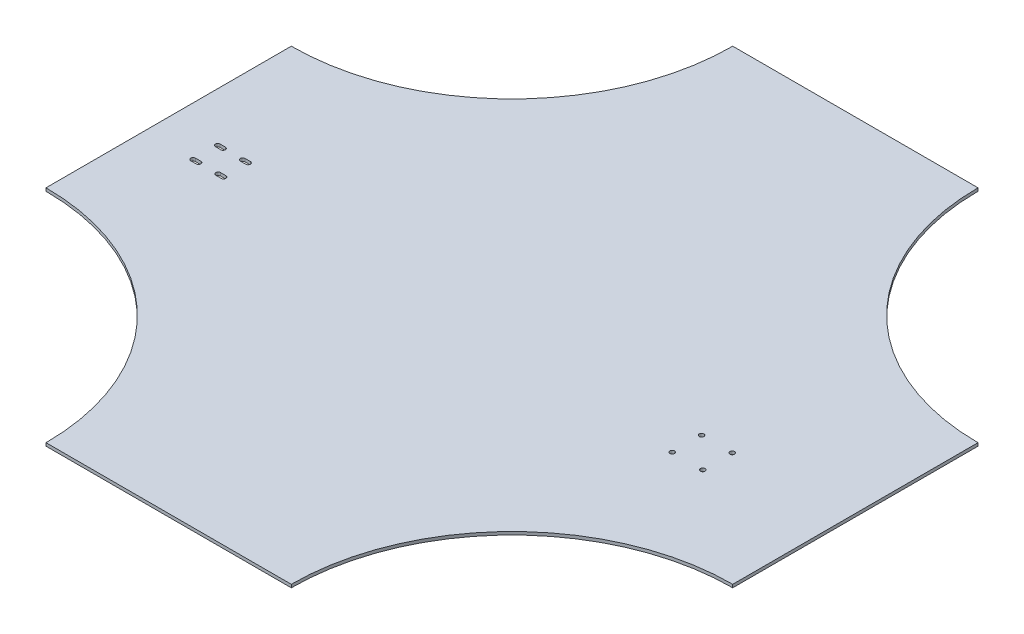
SolidWorks part; units mm, degrees
ref_plane "Front Plane" through (0, 0, 0) normal (0, 0, 1) x (1, 0, 0)
ref_plane "Top Plane" through (0, 0, 0) normal (0, 1, 0) x (1, 0, 0)
ref_plane "Right Plane" through (0, 0, 0) normal (1, 0, 0) x (0, 0, -1)
sketch "Sketch1" plane through (0, 0, 0) normal (0, 1, 0) x (1, 0, 0)
  line L9 (-127, -355.6) -> (127, -355.6)
  line L10 (-355.6, -127) -> (-355.6, 127)
  line L11 (-127, 355.6) -> (127, 355.6)
  line L12 (355.6, -127) -> (355.6, 127)
  line L13 (-193.9554, -193.9554) -> (193.9554, 193.9554) construction
  line L14 (-193.9554, 193.9554) -> (193.9554, -193.9554) construction
  arc A8 (-355.6, 127) -> (-127, 355.6) centre (-355.6, 355.6) ccw
  arc A9 (127, 355.6) -> (355.6, 127) centre (355.6, 355.6) ccw
  arc A10 (355.6, -127) -> (127, -355.6) centre (355.6, -355.6) ccw
  arc A11 (-127, -355.6) -> (-355.6, -127) centre (-355.6, -355.6) ccw
  point P0 (0, 0)
  point P1 (0, 0)
  point P2 (0, 0)
  dimension "D3" = 457.2
  dimension "D4" = 457.2
  dimension "D5" = 457.2
  dimension "D6" = 457.2
  dimension "D1" = 711.2
  dimension "D2" = 711.2
extrude "Boss-Extrude1" add sketch "Sketch1" along normal blind 3.175
sketch "Sketch2" plane through (0, 3.175, 0) normal (0, 1, 0) x (1, 0, 0)
  line L0 (-304.8, 2.413) -> (-299.212, 2.413)
  line L1 (-304.8, -22.987) -> (-299.212, -22.987)
  line L2 (-299.212, -2.413) -> (-304.8, -2.413)
  line L3 (-278.892, -2.413) -> (-273.304, -2.413)
  line L4 (-278.892, -22.987) -> (-273.304, -22.987)
  line L5 (-273.304, 2.413) -> (-278.892, 2.413)
  line L6 (-299.212, -27.813) -> (-304.8, -27.813)
  line L7 (-355.6, 127) -> (-355.6, -127) construction
  line L8 (-273.304, -27.813) -> (-278.892, -27.813)
  arc A0 (-299.212, -2.413) -> (-299.212, 2.413) centre (-299.212, 0) ccw
  arc A1 (-273.304, -2.413) -> (-273.304, 2.413) centre (-273.304, 0) ccw
  arc A2 (-273.304, -27.813) -> (-273.304, -22.987) centre (-273.304, -25.4) ccw
  arc A3 (-299.212, -27.813) -> (-299.212, -22.987) centre (-299.212, -25.4) ccw
  arc A4 (-278.892, 2.413) -> (-278.892, -2.413) centre (-278.892, 0) ccw
  arc A5 (-304.8, 2.413) -> (-304.8, -2.413) centre (-304.8, 0) ccw
  arc A6 (-304.8, -22.987) -> (-304.8, -27.813) centre (-304.8, -25.4) ccw
  arc A7 (-278.892, -22.987) -> (-278.892, -27.813) centre (-278.892, -25.4) ccw
  dimension "D1" = 4.826
  dimension "D2" = 4.826
  dimension "D3" = 4.826
  dimension "D4" = 4.826
  dimension "D5" = 4.826
  dimension "D6" = 4.826
  dimension "D7" = 4.826
  dimension "D8" = 4.826
  dimension "D9" = 5.588
  dimension "D10" = 5.588
  dimension "D11" = 5.588
  dimension "D12" = 5.588
  dimension "D13" = 20.32
  dimension "D14" = 20.32
  dimension "D15" = 25.4
  dimension "D16" = 25.4
  dimension "D17" = 0
  dimension "D18" = 50.8
extrude "Cut-Extrude1" cut sketch "Sketch2" against normal through all both and the other way through all
sketch "Sketch4" plane through (0, 3.175, 0) normal (0, 1, 0) x (1, 0, 0)
  circle A0 centre (237.49, -9.4302) radius 2.413
  circle A1 centre (205.74, -9.4302) radius 2.413
  circle A2 centre (237.49, -39.9102) radius 2.413
  circle A3 centre (205.74, -39.9102) radius 2.413
extrude "Cut-Extrude2" cut sketch "Sketch4" against normal through all
